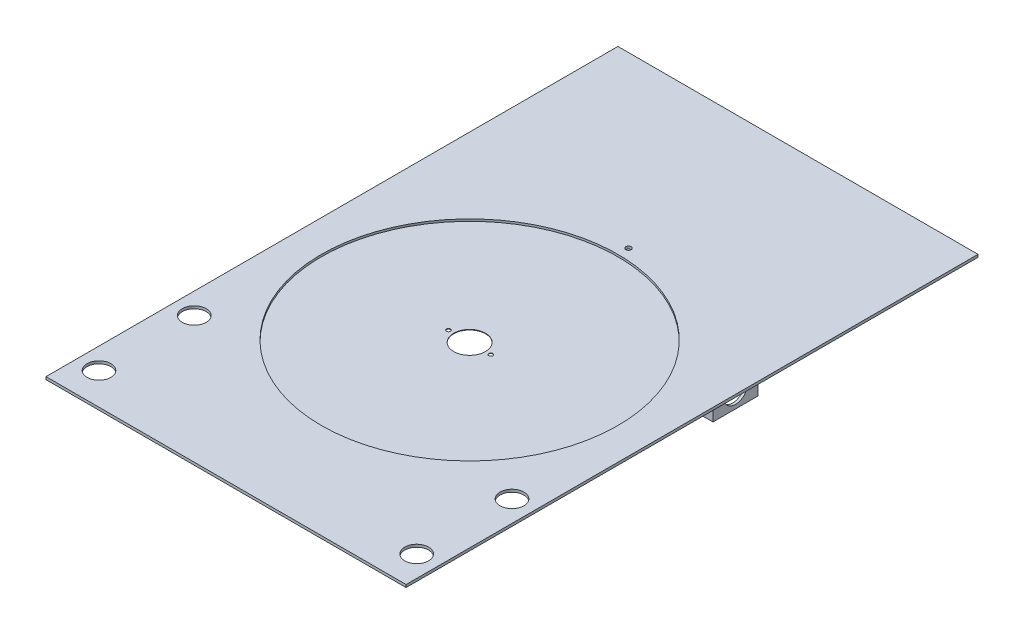
SolidWorks part; units mm, degrees
ref_plane "Front Plane" through (0, 0, 0) normal (0, 0, 1) x (1, 0, 0)
ref_plane "Top Plane" through (0, 0, 0) normal (0, 1, 0) x (1, 0, 0)
ref_plane "Right Plane" through (0, 0, 0) normal (1, 0, 0) x (0, 0, -1)
sketch "Sketch1" plane through (0, 0, 0) normal (0, 1, 0) x (1, 0, 0)
  line L1 (-215.9, 342.9) -> (215.9, 342.9)
  line L2 (-215.9, 342.9) -> (-215.9, -342.9)
  line L3 (-215.9, -342.9) -> (215.9, -342.9)
  line L4 (215.9, 342.9) -> (215.9, -342.9)
  line L5 (-215.9, 342.9) -> (215.9, -342.9) construction
  line L6 (-215.9, -342.9) -> (215.9, 342.9) construction
  point P0 (0, 0)
  dimension "D1" = 431.8
  dimension "D2" = 685.8
extrude "Boss-Extrude1" add sketch "Sketch1" along normal blind 3.175
sketch "Sketch2" plane through (0, 3.175, 0) normal (0, 1, 0) x (1, 0, 0)
  line L0 (0, -342.9) -> (0, 342.9) construction
  line L1 (-215.9, -342.9) -> (215.9, -342.9) construction
  line L2 (215.9, 342.9) -> (-215.9, 342.9) construction
  line L3 (-215.9, 342.9) -> (-215.9, -342.9) construction
  circle A0 centre (-190.5, -304.8) radius 14.2875
  circle A1 centre (-190.5, -190.5) radius 14.2875
  circle A2 centre (190.5, -304.8) radius 14.2875
  circle A3 centre (190.5, -190.5) radius 14.2875
  dimension "D1" = 28.575
  dimension "D2" = 28.575
  dimension "D3" = 38.1
  dimension "D4" = 114.3
  dimension "D5" = 25.4
extrude "Cut-Extrude1" cut sketch "Sketch2" against normal through all
sketch "Sketch3" plane through (0, 0, 0) normal (0, -1, 0) x (-1, 0, 0)
  line L1 (29.8706, 270.2084) -> (-24.7394, 270.2084)
  line L2 (29.8706, 270.2084) -> (29.8706, 216.2334)
  line L3 (29.8706, 216.2334) -> (-24.7394, 216.2334)
  line L4 (-24.7394, 270.2084) -> (-24.7394, 216.2334)
  line L5 (29.8706, 270.2084) -> (-24.7394, 216.2334) construction
  line L6 (29.8706, 216.2334) -> (-24.7394, 270.2084) construction
  point P0 (2.5656, 243.2209)
  dimension "D1" = 53.975
  dimension "D2" = 54.61
extrude "Boss-Extrude2" add sketch "Sketch3" along normal blind 203.2
fillet "Fillet1" radius 20.32 4 edges at (24.7394, 0, -243.2209) (-2.5656, 0, -270.2084) (-2.5656, 0, -216.2334) (-29.8706, 0, -243.2209)
sketch "Sketch4" plane through (0, -203.2, 0) normal (0, -1, 0) x (-1, 0, 0)
  line L0 (-24.7394, 216.2334) -> (29.8706, 216.2334) construction
  line L1 (26.6956, 267.0334) -> (-21.5644, 267.0334)
  line L2 (26.6956, 267.0334) -> (26.6956, 219.4084)
  line L3 (26.6956, 219.4084) -> (-21.5644, 219.4084)
  line L4 (-21.5644, 267.0334) -> (-21.5644, 219.4084)
  line L5 (26.6956, 267.0334) -> (-21.5644, 219.4084) construction
  line L6 (26.6956, 219.4084) -> (-21.5644, 267.0334) construction
  line L7 (29.8706, 270.2084) -> (-24.7394, 270.2084) construction
  line L8 (29.8706, 216.2334) -> (29.8706, 270.2084) construction
  line L9 (-24.7394, 270.2084) -> (-24.7394, 216.2334) construction
  point P0 (2.5656, 243.2209)
  dimension "D1" = 3.175
  dimension "D2" = 3.175
  dimension "D3" = 3.175
  dimension "D4" = 3.175
extrude "Cut-Extrude2" cut sketch "Sketch4" against normal blind 203.2
sketch "Sketch5" plane through (-29.8706, 0, 0) normal (-1, 0, 0) x (0, 0, 1)
  line L0 (-216.2334, -203.2) -> (-216.2334, -20.32) construction
  line L1 (-216.2334, -203.2) -> (-270.2084, -203.2) construction
  circle A0 centre (-243.2209, -184.15) radius 14.2875
  dimension "D1" = 28.575
  dimension "D2" = 26.9875
  dimension "D3" = 19.05
extrude "Cut-Extrude3" cut sketch "Sketch5" against normal blind 203.2
sketch "Sketch6" plane through (0, 3.175, 0) normal (0, 1, 0) x (1, 0, 0)
  circle A0 centre (0, -50.8) radius 177.8
  dimension "D1" = 355.6
  dimension "D2" = 50.8
extrude "Cut-Extrude4" cut sketch "Sketch6" against normal blind 2.54
sketch "Sketch7" plane through (0, 0.635, 0) normal (0, 1, 0) x (1, 0, 0)
  circle A0 centre (25.4, -50.8) radius 2.3812
  circle A1 centre (0, -50.8) radius 177.8 construction
  circle A2 centre (0, -50.8) radius 177.8 construction
  circle A3 centre (-25.4, -50.8) radius 2.3812
  circle A4 centre (0, -50.8) radius 25.4 construction
  circle A5 centre (0, -50.8) radius 19.05
  dimension "D1" = 4.7625
  dimension "D2" = 4.7625
  dimension "D3" = 50.8
  dimension "D4" = 38.1
extrude "Cut-Extrude5" cut sketch "Sketch7" against normal through all
sketch "Sketch8" plane through (0, 3.175, 0) normal (0, 1, 0) x (1, 0, 0)
  circle A0 centre (0, 139.7) radius 3.175
  circle A1 centre (0, -50.8) radius 19.05 construction
  dimension "D1" = 6.35
  dimension "D2" = 190.5
extrude "Cut-Extrude6" cut sketch "Sketch8" against normal through all
